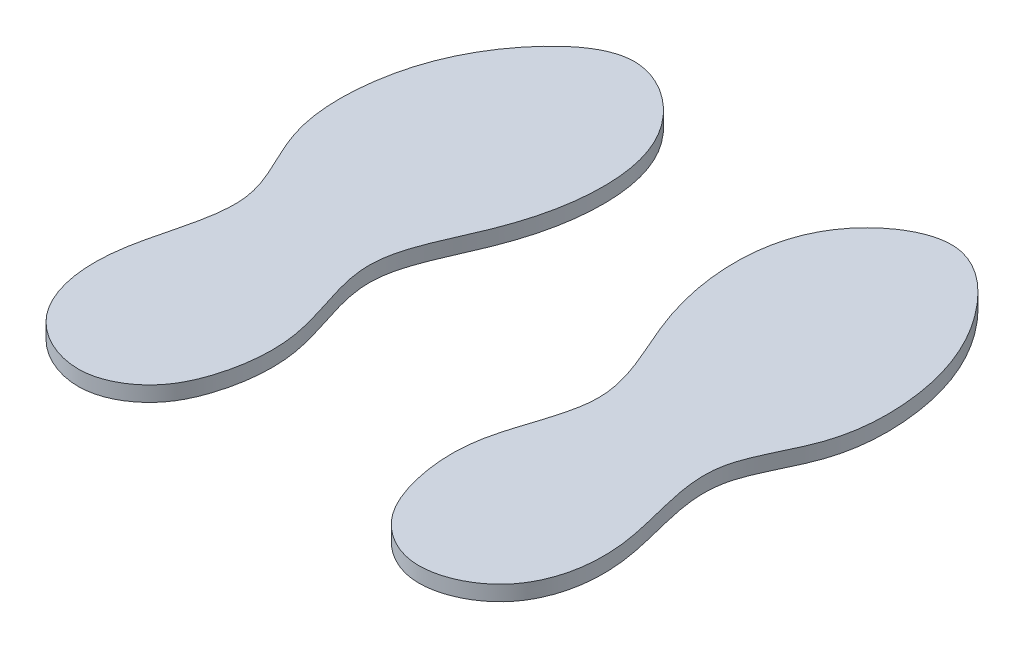
SolidWorks part; units mm, degrees
ref_plane "Front Plane" through (0, 0, 0) normal (0, 0, 1) x (1, 0, 0)
ref_plane "Top Plane" through (0, 0, 0) normal (0, 1, 0) x (1, 0, 0)
ref_plane "Right Plane" through (0, 0, 0) normal (1, 0, 0) x (0, 0, -1)
sketch "Sketch4" plane through (0, 0, 0) normal (0, 1, 0) x (1, 0, 0)
  line L0 (56.4057, 205.7862) -> (275.739, 205.7862) construction
  line L1 (106.5441, 392.4491) -> (106.5441, 34.2507) construction
  line L2 (43.5276, 392.4491) -> (169.5606, 392.4491) construction
  line L3 (43.5276, 392.4491) -> (43.5276, 34.2507) construction
  line L4 (43.5276, 34.2507) -> (169.5606, 34.2507) construction
  line L5 (169.5606, 392.4491) -> (169.5606, 34.2507) construction
  line L6 (58.6245, 364.3793) -> (149.0935, 364.3793) construction
  line L7 (0, 409.6507) -> (0, 0) construction
  line L8 (43.5276, 303.4815) -> (179.4649, 290.0428) construction
  line L10 (56.1909, 249.4139) -> (174.4849, 237.7195) construction
  line L12 (75.6048, 190.165) -> (155.5664, 190.165) construction
  line L14 (60.6595, 126.0842) -> (166.5312, 115.6178) construction
  line L16 (63.3872, 78.3209) -> (161.7971, 68.5921) construction
  line L18 (76.1578, 52.0606) -> (151.5436, 52.0606) construction
  spline S0 degree 3 poles (48.6704, 365.5963) (106.3639, 405.5539) (161.1746, 358.1666) (182.8239, 300.1421) (179.3716, 236.9598) (143.3222, 183.7737) (170.2868, 125.5561) (167.4369, 76.3404) (147.6562, 42.9463) (109.8754, 26.3151) (74.5548, 48.6354) (59.7412, 83.871) (56.2023, 132.5815) (86.9019, 189.3363) (54.2529, 247.0242) (39.3999, 305.1123) (48.6704, 365.5963) (106.3639, 405.5539) (161.1746, 358.1666) knots -0.206989 -0.140857 -0.066138 0 0.060706 0.156337 0.218931 0.279881 0.369615 0.425901 0.449068 0.506703 0.548648 0.583423 0.640398 0.71876 0.793011 0.859143 0.933862 1 1.060706 1.156337 1.218931 only from (106.5441, 392.4491) to (106.5441, 392.4491)
  spline S1 degree 3 poles (-48.6704, 365.5963) (-106.3639, 405.5539) (-161.1746, 358.1666) (-182.8239, 300.1421) (-179.3716, 236.9598) (-143.3222, 183.7737) (-170.2868, 125.5561) (-167.4369, 76.3404) (-147.6562, 42.9463) (-109.8754, 26.3151) (-74.5548, 48.6354) (-59.7412, 83.871) (-56.2023, 132.5815) (-86.9019, 189.3363) (-54.2529, 247.0242) (-39.3999, 305.1123) (-48.6704, 365.5963) (-106.3639, 405.5539) (-161.1746, 358.1666) knots -0.206989 -0.140857 -0.066138 0 0.060706 0.156337 0.218931 0.279881 0.369615 0.425901 0.449068 0.506703 0.548648 0.583423 0.640398 0.71876 0.793011 0.859143 0.933862 1 1.060706 1.156337 1.218931 only from (-106.5441, 392.4491) to (-106.5441, 392.4491)
extrude "Boss-Extrude4" add sketch "Sketch4" along normal blind 10
